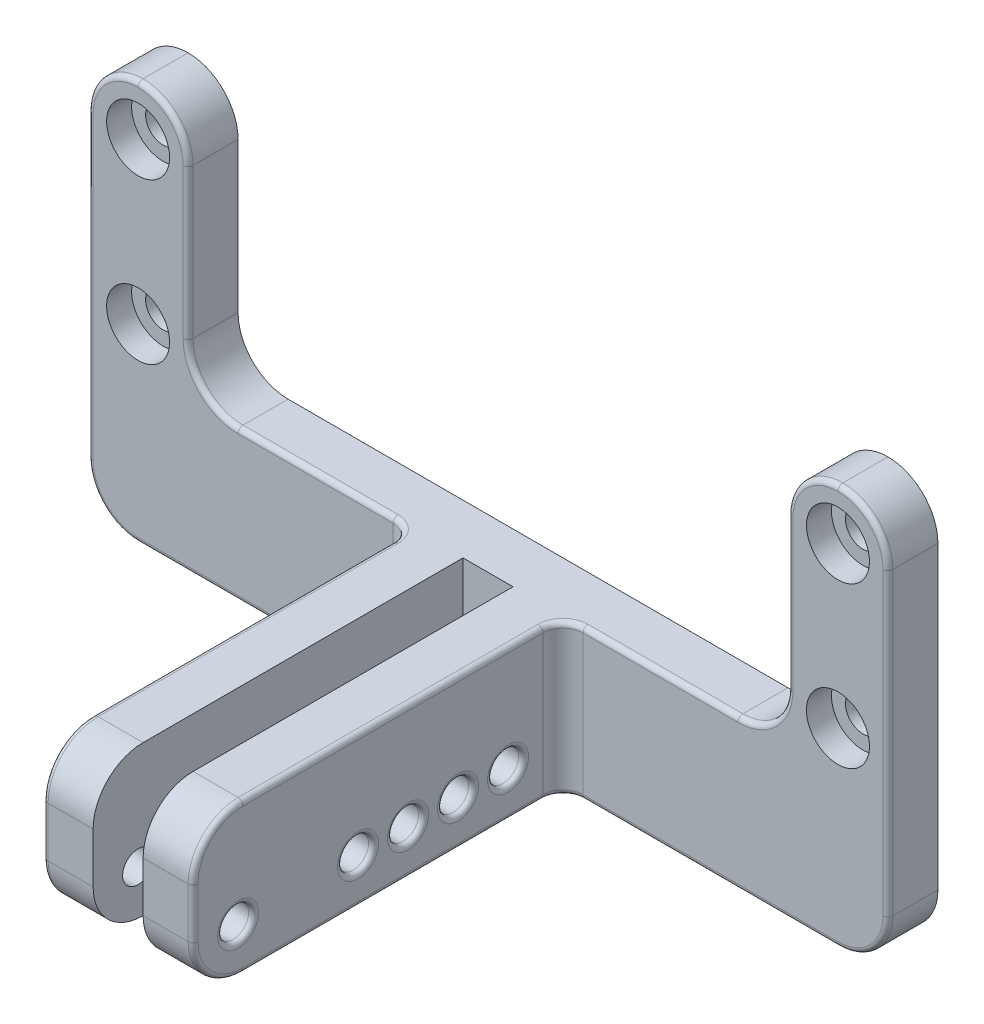
SolidWorks part; units mm, degrees
ref_plane "正面" through (0, 0, 0) normal (0, 0, 1) x (1, 0, 0)
ref_plane "平面" through (0, 0, 0) normal (0, 1, 0) x (1, 0, 0)
ref_plane "右側面" through (0, 0, 0) normal (1, 0, 0) x (0, 0, -1)
sketch "ｽｹｯﾁ1" plane through (0, 0, 0) normal (0, 0, 1) x (1, 0, 0)
  line L1 (40, 20) -> (-40, 20)
  line L2 (40, 20) -> (40, -20)
  line L3 (40, -20) -> (-40, -20)
  line L4 (-40, 20) -> (-40, -20)
  line L5 (40, 20) -> (-40, -20) construction
  line L6 (40, -20) -> (-40, 20) construction
  point P0 (0, 0)
  dimension "D1" = 80
  dimension "D2" = 40
extrude "ﾎﾞｽ - 押し出し1" add sketch "ｽｹｯﾁ1" along normal blind 5
sketch "ｽｹｯﾁ2" plane through (0, 0, 0) normal (0, 0, 1) x (1, 0, 0)
  line L0 (40, -20) -> (40, 20) construction
  line L1 (40, 20) -> (-40, 20) construction
  line L2 (0, 20) -> (0, -20) construction
  line L3 (-40, -20) -> (40, -20) construction
  circle A0 centre (35, 15) radius 1.75
  circle A1 centre (35, -1) radius 1.75
  circle A2 centre (-35, 15) radius 1.75
  circle A3 centre (-35, -1) radius 1.75
  dimension "D1" = 3.5
  dimension "D2" = 3.5
  dimension "D3" = 5
  dimension "D4" = 5
  dimension "D5" = 0
  dimension "D6" = 16
extrude "ｶｯﾄ - 押し出し1" cut sketch "ｽｹｯﾁ2" along normal through all
sketch "ｽｹｯﾁ3" plane through (0, 0, 5) normal (0, 0, 1) x (1, 0, 0)
  line L0 (0, 20) -> (0, -20) construction
  line L1 (40, 20) -> (-40, 20) construction
  line L2 (-40, -20) -> (40, -20) construction
  line L3 (7.5, -20) -> (7.5, -5)
  line L4 (-2.5, -20) -> (-7.5, -20)
  line L5 (-2.5, -20) -> (-2.5, -5)
  line L6 (-2.5, -5) -> (-7.5, -5)
  line L7 (-7.5, -20) -> (-7.5, -5)
  line L8 (2.5, -5) -> (7.5, -5)
  line L9 (2.5, -20) -> (2.5, -5)
  line L10 (2.5, -20) -> (7.5, -20)
  dimension "D1" = 2.5
  dimension "D2" = 15
  dimension "D3" = 5
extrude "ﾎﾞｽ - 押し出し2" add sketch "ｽｹｯﾁ3" along normal blind 37
sketch "ｽｹｯﾁ4" plane through (-7.5, 0, 0) normal (-1, 0, 0) x (0, 0, 1)
  line L0 (42, -20) -> (5, -20) construction
  line L1 (5, -5) -> (5, -20) construction
  circle A0 centre (10.5, -15.5) radius 1.55
  circle A1 centre (37.5, -15.5) radius 1.55
  circle A2 centre (15.5, -15.5) radius 1.55
  circle A3 centre (20.5, -15.5) radius 1.55
  circle A4 centre (25.5, -15.5) radius 1.55
  dimension "D1" = 3.1
  dimension "D2" = 5.5
  dimension "D3" = 3.1
  dimension "D4" = 27
  dimension "D5" = 4.5
  dimension "D6" = 4
extrude "ｶｯﾄ - 押し出し2" cut sketch "ｽｹｯﾁ4" against normal through all
sketch "ｽｹｯﾁ5" plane through (0, 0, 0) normal (0, 0, 1) x (1, 0, 0)
  line L0 (40, 20) -> (-40, 20) construction
  line L1 (30, 20) -> (-30, 20)
  line L2 (30, 20) -> (30, -5)
  line L3 (30, -5) -> (-30, -5)
  line L4 (-30, 20) -> (-30, -5)
  line L5 (40, -20) -> (40, 20) construction
  line L6 (-40, 20) -> (-40, -20) construction
  dimension "D1" = 25
  dimension "D2" = 10
  dimension "D3" = 10
extrude "ｶｯﾄ - 押し出し3" cut sketch "ｽｹｯﾁ5" along normal blind 5
fillet "ﾌｨﾚｯﾄ1" radius 5 4 edges at (5, -5, 42) (-5, -5, 42) (5, -20, 42) (-5, -20, 42)
fillet "ﾌｨﾚｯﾄ2" radius 5 8 edges at (-30, -5, 2.5) (30, -5, 2.5) (30, 20, 2.5) (40, 20, 2.5) (40, -20, 2.5) (-40, -20, 2.5) (-30, 20, 2.5) (-40, 20, 2.5)
fillet "ﾌｨﾚｯﾄ3" radius 2 2 edges at (7.5, -12.5, 5)
fillet "ﾌｨﾚｯﾄ4" radius 0.5 40 edges at (8.0858, -5, 5.5858) (17.25, -5, 5) (28.5355, -3.5355, 5) (30, 7.5, 5) (31.4645, 18.5355, 5) (38.5355, 18.5355, 5) (40, 0, 5) (38.5355, -18.5355, 5) (8.0858, -20, 5.5858) (-8.0858, -20, 5.5858) (-38.5355, -18.5355, 5) (-40, 0, 5) (-38.5355, 18.5355, 5) (-31.4645, 18.5355, 5) (-30, 7.5, 5) (-28.5355, -3.5355, 5) (-17.25, -5, 5) (-8.0858, -5, 5.5858) (7.5, -18.5355, 40.5355) (7.5, -12.5, 42) (7.5, -6.4645, 40.5355) (7.5, -5, 22) (7.5, -20, 22) (7.5, -17.05, 10.5) (7.5, -17.05, 37.5) (-7.5, -6.4645, 40.5355) (-7.5, -12.5, 42) (-7.5, -18.5355, 40.5355) (-7.5, -5, 22) (-7.5, -15.5, 12.05) (-7.5, -15.5, 39.05) (7.5, -17.05, 15.5) (7.5, -17.05, 20.5) (7.5, -17.05, 25.5) (-7.5, -15.5, 17.05) (-7.5, -15.5, 22.05) (-7.5, -15.5, 27.05)
sketch "ｽｹｯﾁ6" plane through (0, 0, 5) normal (0, 0, 1) x (1, 0, 0)
  line L0 (0, 0) -> (0, -20) construction
  line L1 (-2.5, -20) -> (2.5, -20) construction
  circle A0 centre (-35, 15) radius 3.15
  circle A1 centre (-35, -1) radius 3.15
  circle A2 centre (35, -1) radius 3.15
  circle A3 centre (35, 15) radius 3.15
  dimension "D1" = 6.3
  dimension "D2" = 6.3
extrude "ｶｯﾄ - 押し出し4" cut sketch "ｽｹｯﾁ6" against normal blind 2.5
